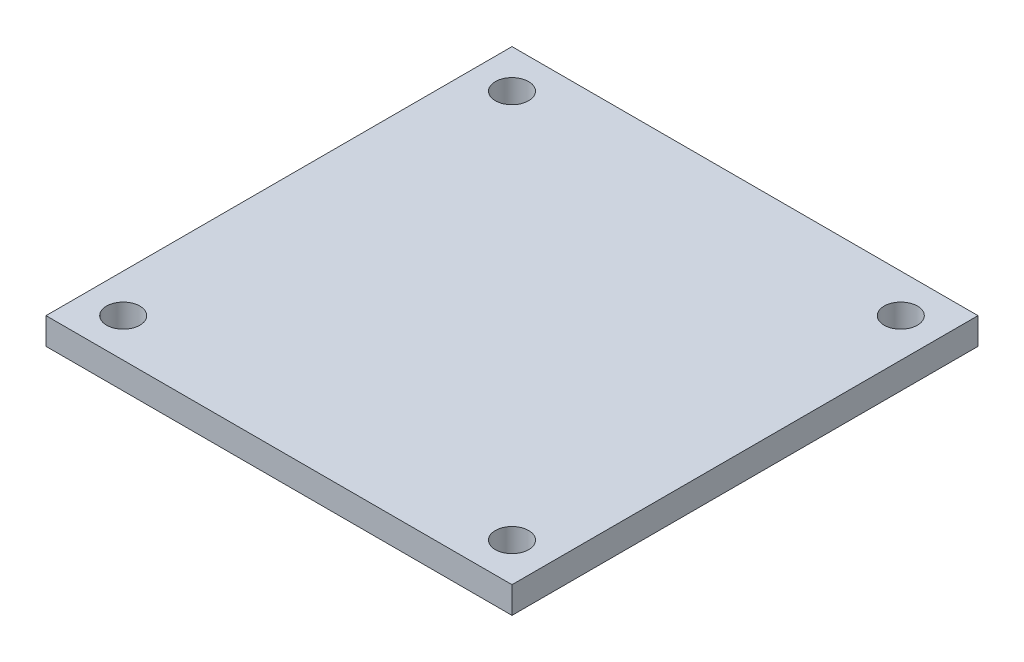
SolidWorks part; units mm, degrees
ref_plane "Front Plane" through (0, 0, 0) normal (0, 0, 1) x (1, 0, 0)
ref_plane "Top Plane" through (0, 0, 0) normal (0, 1, 0) x (1, 0, 0)
ref_plane "Right Plane" through (0, 0, 0) normal (1, 0, 0) x (0, 0, -1)
sketch "Sketch1" plane through (0, 0, 0) normal (0, 1, 0) x (1, 0, 0)
  line L1 (17.5, 17.5) -> (-17.5, 17.5)
  line L2 (17.5, 17.5) -> (17.5, -17.5)
  line L3 (17.5, -17.5) -> (-17.5, -17.5)
  line L4 (-17.5, 17.5) -> (-17.5, -17.5)
  line L5 (17.5, 17.5) -> (-17.5, -17.5) construction
  line L6 (17.5, -17.5) -> (-17.5, 17.5) construction
  point P0 (0, 0)
  dimension "D1" = 35
  dimension "D2" = 35
extrude "Boss-Extrude1" add sketch "Sketch1" along normal blind 2
sketch "Sketch2" plane through (0, 2, 0) normal (0, 1, 0) x (1, 0, 0)
  line L0 (0, -17.5) -> (0, 17.5)
  line L1 (-17.5, -17.5) -> (17.5, -17.5) construction
  line L2 (17.5, 17.5) -> (-17.5, 17.5) construction
  line L3 (17.5, 0) -> (-17.5, 0)
  line L4 (17.5, -17.5) -> (17.5, 17.5) construction
  line L5 (-17.5, 17.5) -> (-17.5, -17.5) construction
  circle A0 centre (-14.6, -14.6) radius 1.25
  circle A1 centre (14.6, -14.6) radius 1.25
  circle A2 centre (-14.6, 14.6) radius 1.25
  circle A3 centre (14.6, 14.6) radius 1.25
  dimension "D1" = 32.1
  dimension "D2" = 32.1
extrude "Cut-Extrude1" cut sketch "Sketch2" against normal through all contours A1 | A0 | A2 | A3 region at (14.6, 2, 14.6)
